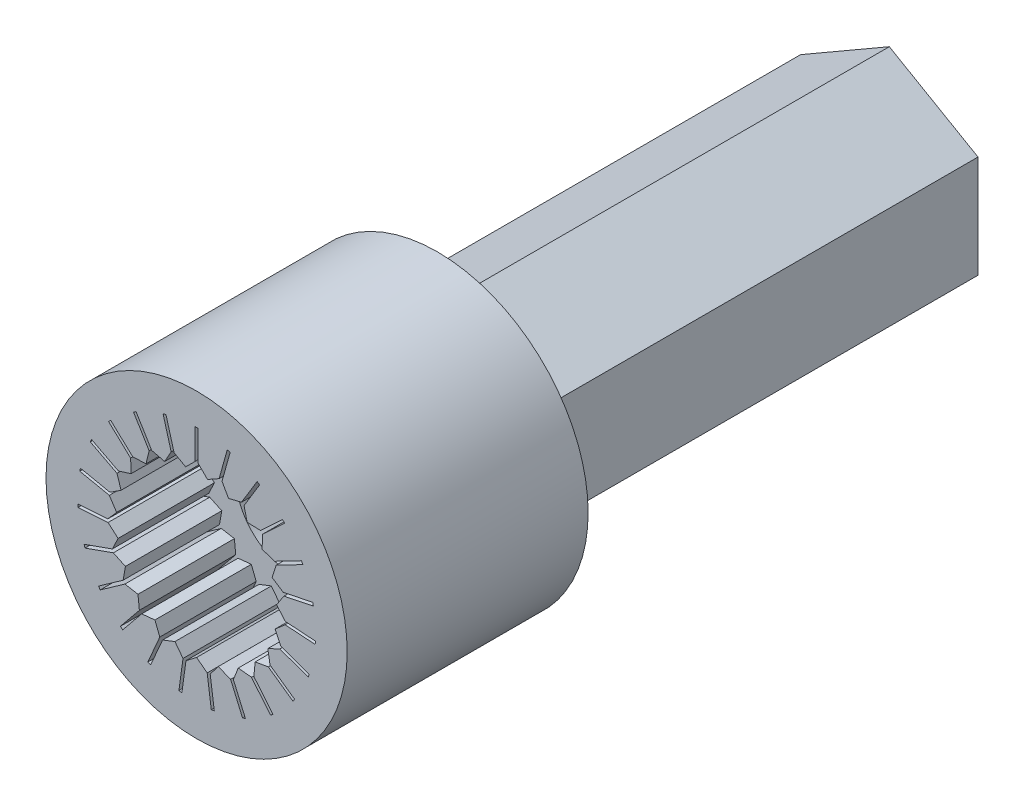
SolidWorks part; units mm, degrees
ref_plane "正面" through (0, 0, 0) normal (0, 0, 1) x (1, 0, 0)
ref_plane "平面" through (0, 0, 0) normal (0, 1, 0) x (1, 0, 0)
ref_plane "右側面" through (0, 0, 0) normal (1, 0, 0) x (0, 0, -1)
sketch "ｽｹｯﾁ1" plane through (0, 0, 0) normal (0, 0, 1) x (1, 0, 0)
  line L1 (0, 3.4) -> (-2.9445, 1.7)
  line L2 (-2.9445, 1.7) -> (-2.9445, -1.7)
  line L3 (-2.9445, -1.7) -> (0, -3.4)
  line L4 (0, -3.4) -> (2.9445, -1.7)
  line L5 (2.9445, -1.7) -> (2.9445, 1.7)
  line L6 (2.9445, 1.7) -> (0, 3.4)
  circle A0 centre (0, 0) radius 2.9445 construction
  dimension "D1" = 6.8
extrude "ﾎﾞｽ - 押し出し1" add sketch "ｽｹｯﾁ1" along normal blind 15
sketch "ｽｹｯﾁ6" plane through (0, 0, 15) normal (0, 0, 1) x (1, 0, 0)
  circle A0 centre (0, 0) radius 5
  dimension "D1" = 10
extrude "ﾎﾞｽ - 押し出し3" add sketch "ｽｹｯﾁ6" along normal blind 8
sketch "ｽｹｯﾁ5" plane through (0, 0, 23) normal (0, 0, 1) x (1, 0, 0)
  line L0 (-0.3625, 2.6375) -> (0, 3) construction
  line L1 (0, 3) -> (0.3625, 2.6375) construction
  line L2 (-0.3625, 2.6375) -> (0, 0) construction
  line L3 (0, 0) -> (0.3625, 2.6375) construction
  line L4 (0, 3) -> (0, 0) construction
  line L5 (-0.05, 2.95) -> (-0.05, 3.95)
  line L6 (-0.05, 3.95) -> (0.05, 3.95)
  line L7 (0.05, 3.95) -> (0.05, 2.95)
  line L8 (-0.05, 2.95) -> (0.05, 2.95) construction
  line L9 (-0.3625, 2.6375) -> (-0.05, 2.95)
  line L10 (-0.05, 2.95) -> (0.05, 2.95) construction
  line L11 (0.3625, 2.6375) -> (0.05, 2.95)
  line L12 (0.3625, 2.6375) -> (0.7478, 2.8541)
  line L13 (0.7478, 2.8541) -> (1.0176, 3.817)
  line L14 (1.1138, 3.79) -> (0.844, 2.8271)
  line L15 (1.0607, 2.4419) -> (0.844, 2.8271)
  line L16 (1.0176, 3.817) -> (1.1138, 3.79)
  line L17 (1.0607, 2.4419) -> (1.4901, 2.5465)
  line L18 (1.4901, 2.5465) -> (2.0096, 3.4009)
  line L19 (2.0951, 3.349) -> (1.5755, 2.4946)
  line L20 (1.6801, 2.0652) -> (1.5755, 2.4946)
  line L21 (2.0096, 3.4009) -> (2.0951, 3.349)
  line L22 (1.6801, 2.0652) -> (2.1218, 2.0501)
  line L23 (2.1218, 2.0501) -> (2.8527, 2.7326)
  line L24 (2.9209, 2.6595) -> (2.1901, 1.977)
  line L25 (2.175, 1.5353) -> (2.1901, 1.977)
  line L26 (2.8527, 2.7326) -> (2.9209, 2.6595)
  line L27 (2.175, 1.5353) -> (2.5963, 1.4016)
  line L28 (2.5963, 1.4016) -> (3.4841, 1.8617)
  line L29 (3.5301, 1.7729) -> (2.6423, 1.3128)
  line L30 (2.5086, 0.8915) -> (2.6423, 1.3128)
  line L31 (3.4841, 1.8617) -> (3.5301, 1.7729)
  line L32 (2.5086, 0.8915) -> (2.8781, 0.6491)
  line L33 (2.8781, 0.6491) -> (3.8572, 0.8526)
  line L34 (3.8776, 0.7547) -> (2.8985, 0.5512)
  line L35 (2.6561, 0.1817) -> (2.8985, 0.5512)
  line L36 (3.8572, 0.8526) -> (3.8776, 0.7547)
  line L37 (2.6561, 0.1817) -> (2.9465, -0.1514)
  line L38 (2.9465, -0.1514) -> (3.9442, -0.2197)
  line L39 (3.9374, -0.3194) -> (2.9397, -0.2512)
  line L40 (2.6066, -0.5417) -> (2.9397, -0.2512)
  line L41 (3.9442, -0.2197) -> (3.9374, -0.3194)
  line L42 (2.6066, -0.5417) -> (2.7964, -0.9408)
  line L43 (2.7964, -0.9408) -> (3.7387, -1.2757)
  line L44 (3.7052, -1.3699) -> (2.7629, -1.035)
  line L45 (2.3638, -1.2248) -> (2.7629, -1.035)
  line L46 (3.7387, -1.2757) -> (3.7052, -1.3699)
  line L47 (2.3638, -1.2248) -> (2.4389, -1.6604)
  line L48 (2.4389, -1.6604) -> (3.2559, -2.237)
  line L49 (3.1982, -2.3187) -> (2.3812, -1.7421)
  line L50 (1.9457, -1.8171) -> (2.3812, -1.7421)
  line L51 (3.2559, -2.237) -> (3.1982, -2.3187)
  line L52 (1.9457, -1.8171) -> (1.9005, -2.2568)
  line L53 (1.9005, -2.2568) -> (2.5316, -3.0325)
  line L54 (2.454, -3.0956) -> (1.8229, -2.3199)
  line L55 (1.3833, -2.2747) -> (1.8229, -2.3199)
  line L56 (2.5316, -3.0325) -> (2.454, -3.0956)
  line L57 (1.3833, -2.2747) -> (1.2211, -2.6859)
  line L58 (1.2211, -2.6859) -> (1.6195, -3.6031)
  line L59 (1.5278, -3.6429) -> (1.1294, -2.7257)
  line L60 (0.7183, -2.5636) -> (1.1294, -2.7257)
  line L61 (1.6195, -3.6031) -> (1.5278, -3.6429)
  line L62 (0.7183, -2.5636) -> (0.4512, -2.9157)
  line L63 (0.4512, -2.9157) -> (0.5874, -3.9064)
  line L64 (0.4883, -3.92) -> (0.3522, -2.9293)
  line L65 (0, -2.6623) -> (0.3522, -2.9293)
  line L66 (0.5874, -3.9064) -> (0.4883, -3.92)
  line L67 (0, -2.6623) -> (-0.3522, -2.9293)
  line L68 (-0.3522, -2.9293) -> (-0.4883, -3.92)
  line L69 (-0.5874, -3.9064) -> (-0.4512, -2.9157)
  line L70 (-0.7183, -2.5636) -> (-0.4512, -2.9157)
  line L71 (-0.4883, -3.92) -> (-0.5874, -3.9064)
  line L72 (-0.7183, -2.5636) -> (-1.1294, -2.7257)
  line L73 (-1.1294, -2.7257) -> (-1.5278, -3.6429)
  line L74 (-1.6195, -3.6031) -> (-1.2211, -2.6859)
  line L75 (-1.3833, -2.2747) -> (-1.2211, -2.6859)
  line L76 (-1.5278, -3.6429) -> (-1.6195, -3.6031)
  line L77 (-1.3833, -2.2747) -> (-1.8229, -2.3199)
  line L78 (-1.8229, -2.3199) -> (-2.454, -3.0956)
  line L79 (-2.5316, -3.0325) -> (-1.9005, -2.2568)
  line L80 (-1.9457, -1.8171) -> (-1.9005, -2.2568)
  line L81 (-2.454, -3.0956) -> (-2.5316, -3.0325)
  line L82 (-1.9457, -1.8171) -> (-2.3812, -1.7421)
  line L83 (-2.3812, -1.7421) -> (-3.1982, -2.3187)
  line L84 (-3.2559, -2.237) -> (-2.4389, -1.6604)
  line L85 (-2.3638, -1.2248) -> (-2.4389, -1.6604)
  line L86 (-3.1982, -2.3187) -> (-3.2559, -2.237)
  line L87 (-2.3638, -1.2248) -> (-2.7629, -1.035)
  line L88 (-2.7629, -1.035) -> (-3.7052, -1.3699)
  line L89 (-3.7387, -1.2757) -> (-2.7964, -0.9408)
  line L90 (-2.6066, -0.5417) -> (-2.7964, -0.9408)
  line L91 (-3.7052, -1.3699) -> (-3.7387, -1.2757)
  line L92 (-2.6066, -0.5417) -> (-2.9397, -0.2512)
  line L93 (-2.9397, -0.2512) -> (-3.9374, -0.3194)
  line L94 (-3.9442, -0.2197) -> (-2.9465, -0.1514)
  line L95 (-2.6561, 0.1817) -> (-2.9465, -0.1514)
  line L96 (-3.9374, -0.3194) -> (-3.9442, -0.2197)
  line L97 (-2.6561, 0.1817) -> (-2.8985, 0.5512)
  line L98 (-2.8985, 0.5512) -> (-3.8776, 0.7547)
  line L99 (-3.8572, 0.8526) -> (-2.8781, 0.6491)
  line L100 (-2.5086, 0.8915) -> (-2.8781, 0.6491)
  line L101 (-3.8776, 0.7547) -> (-3.8572, 0.8526)
  line L102 (-2.5086, 0.8915) -> (-2.6423, 1.3128)
  line L103 (-2.6423, 1.3128) -> (-3.5301, 1.7729)
  line L104 (-3.4841, 1.8617) -> (-2.5963, 1.4016)
  line L105 (-2.175, 1.5353) -> (-2.5963, 1.4016)
  line L106 (-3.5301, 1.7729) -> (-3.4841, 1.8617)
  line L107 (-2.175, 1.5353) -> (-2.1901, 1.977)
  line L108 (-2.1901, 1.977) -> (-2.9209, 2.6595)
  line L109 (-2.8527, 2.7326) -> (-2.1218, 2.0501)
  line L110 (-1.6801, 2.0652) -> (-2.1218, 2.0501)
  line L111 (-2.9209, 2.6595) -> (-2.8527, 2.7326)
  line L112 (-1.6801, 2.0652) -> (-1.5755, 2.4946)
  line L113 (-1.5755, 2.4946) -> (-2.0951, 3.349)
  line L114 (-2.0096, 3.4009) -> (-1.4901, 2.5465)
  line L115 (-1.0607, 2.4419) -> (-1.4901, 2.5465)
  line L116 (-2.0951, 3.349) -> (-2.0096, 3.4009)
  line L117 (-1.0607, 2.4419) -> (-0.844, 2.8271)
  line L118 (-0.844, 2.8271) -> (-1.1138, 3.79)
  line L119 (-1.0176, 3.817) -> (-0.7478, 2.8541)
  line L120 (-0.3625, 2.6375) -> (-0.7478, 2.8541)
  line L121 (-1.1138, 3.79) -> (-1.0176, 3.817)
  circle A0 centre (0, 0) radius 3 construction
  circle A1 centre (0, 0) radius 2.6623 construction
  point P147 (0, 0)
  dimension "D1" = 6
  dimension "D2" = 7.826
  dimension "D3" = 7.826
  dimension "D4" = 0.1
  dimension "D5" = 1
  dimension "D6" = 23
extrude "ｶｯﾄ - 押し出し5" cut sketch "ｽｹｯﾁ5" against normal blind 3.2
chamfer "面取り1" distance 1 angle 45 6 edges at (1.4722, 2.55, 15) (2.9445, 0, 15) (1.4722, -2.55, 15) (-1.4722, -2.55, 15) (-2.9445, 0, 15) (-1.4722, 2.55, 15)
sketch "ｽｹｯﾁ7" plane through (0, 0, 0) normal (0, 0, -1) x (-1, 0, 0)
  circle A0 centre (0, 0) radius 1.9
  dimension "D1" = 3.8
extrude "ｶｯﾄ - 押し出し6" cut sketch "ｽｹｯﾁ7" against normal through all
equation "\"18.4.300mm\"=18.3"
equation "\"D2@ｽｹｯﾁ5\"=360deg/46"
equation "\"D3@ｽｹｯﾁ5\"=\"D2@ｽｹｯﾁ5\""
